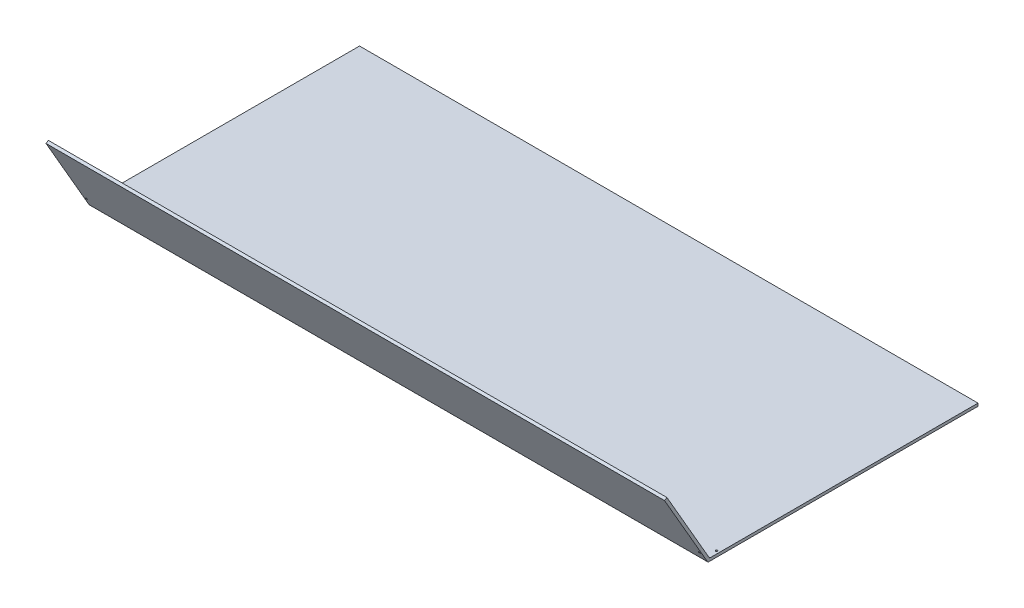
SolidWorks part; units mm, degrees
material "PPE"
ref_plane "Front Plane" through (0, 0, 0) normal (0, 0, 1) x (1, 0, 0)
ref_plane "Top Plane" through (0, 0, 0) normal (0, 1, 0) x (1, 0, 0)
ref_plane "Right Plane" through (0, 0, 0) normal (1, 0, 0) x (0, 0, -1)
sketch "Sketch1" plane through (0, 0, 0) normal (0, 1, 0) x (1, 0, 0)
  line L1 (-525.018, -228.6) -> (525.018, -228.6)
  line L2 (-525.018, -228.6) -> (-525.018, 228.6)
  line L3 (-525.018, 228.6) -> (525.018, 228.6)
  line L4 (525.018, -228.6) -> (525.018, 228.6)
  line L5 (-525.018, -228.6) -> (136.1971, 59.3021) construction
  line L6 (-525.018, 228.6) -> (525.018, -228.6) construction
  line L7 (-525.018, -228.6) -> (525.018, 228.6) construction
  point P0 (0, 0)
  dimension "D4" = 457.2
  dimension "D5" = 1050.036
extrude "Boss-Extrude1" add sketch "Sketch1" along normal blind 4.7625
sketch "Sketch2" plane through (-525.018, 0, 0) normal (-1, 0, 0) x (0, 0, 1)
  line L0 (228.6, 4.7625) -> (228.6, 0) construction
  line L1 (228.6, 4.7625) -> (228.6, 0)
  arc A0 (228.6, 0) -> (228.6, 4.7625) centre (228.6, 2.3813) ccw
extrude "Boss-Extrude2" add sketch "Sketch2" against normal up to surface (1050.036 mm away) up to face at (525.018, 2.3813, 0)
sketch "Sketch6"
  dimension "D1" = 7.9375
  dimension "D2" = 7.9375
  dimension "D3" = 4.7625
extrude "Cut-Extrude1" [suppressed] cut sketch "Sketch6" against normal up to next
sketch "Sketch9" plane through (0, 4.7625, 0) normal (0, 1, 0) x (1, 0, 0)
  line L0 (-520.2555, -210.3923) -> (520.2555, -210.3923) construction
  line L1 (525.018, -228.6) -> (525.018, 228.6) construction
  line L2 (-525.018, -228.6) -> (525.018, -228.6) construction
  circle A0 centre (520.2555, -210.3923) radius 1.5875
  circle A1 centre (-520.2555, -210.3923) radius 1.5875
  point P3 (0, -210.3923)
  dimension "D1" = 3.175
  dimension "D2" = 4.7625
  dimension "D3" = 18.2077
extrude "Cut-Extrude3" cut sketch "Sketch9" against normal through all
pattern_circular "CirPattern1" count 2 every 120 about axis through (525.018, 2.3813, 228.6) along (1, 0, 0) of "Boss-Extrude1", "Cut-Extrude3"
pattern_circular "CirPattern2" [suppressed] count 2 every 120 of bodies 109
sketch "Sketch8" plane through (0, -97.2008, 168.3567) normal (0, 0.5, -0.866) x (-1, 0, 0)
  line L0 (525.018, 573.5622) -> (525.018, 117.737) construction
  line L1 (-525.018, 573.5622) -> (525.018, 573.5622)
  line L2 (-525.018, 573.5622) -> (-525.018, 262.4122)
  line L3 (-525.018, 262.4122) -> (525.018, 262.4122)
  line L4 (525.018, 573.5622) -> (525.018, 262.4122)
  dimension "D1" = 311.15
extrude "Cut-Extrude2" cut sketch "Sketch8" against normal up to next
fillet "Fillet1" radius 2.3813 1 edges at (0, 4.7625, 227.2252)
